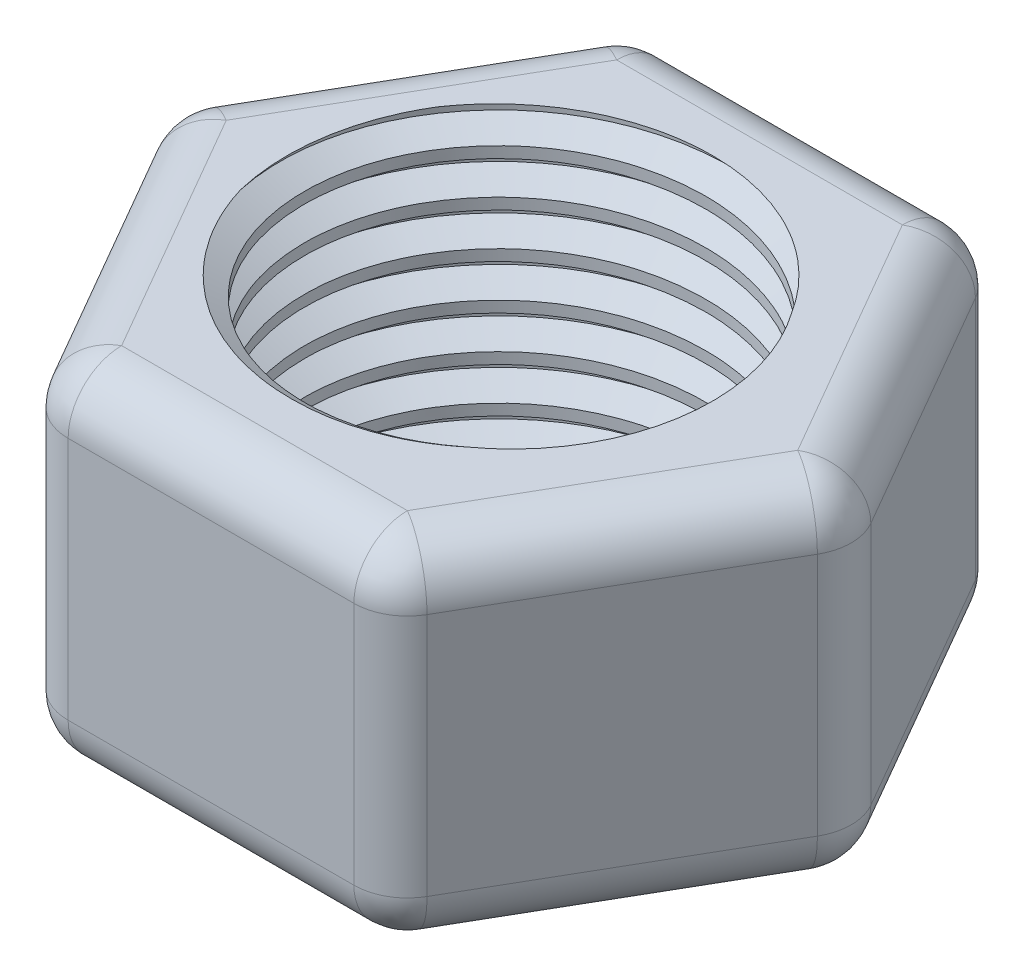
SolidWorks part; units mm, degrees
material "AISI 316 Annealed Stainless Steel Bar (SS)"
ref_plane "Front Plane" through (0, 0, 0) normal (0, 0, 1) x (1, 0, 0)
ref_plane "Top Plane" through (0, 0, 0) normal (0, 1, 0) x (1, 0, 0)
ref_plane "Right Plane" through (0, 0, 0) normal (1, 0, 0) x (0, 0, -1)
sketch "Sketch1" plane through (0, 0, 0) normal (0, 1, 0) x (1, 0, 0)
  line L1 (8.2489, 0) -> (4.1244, 7.1437)
  line L2 (4.1244, 7.1437) -> (-4.1244, 7.1437)
  line L3 (-4.1244, 7.1437) -> (-8.2489, 0)
  line L4 (-8.2489, 0) -> (-4.1244, -7.1437)
  line L5 (-4.1244, -7.1437) -> (4.1244, -7.1437)
  line L6 (4.1244, -7.1437) -> (8.2489, 0)
  circle A0 centre (0, 0) radius 7.1437 construction
  circle A1 centre (0, 0) radius 4.7625
  dimension "D2" = 9.525
  dimension "D1" = 14.2875
extrude "Boss-Extrude1" add sketch "Sketch1" along normal blind 8.3344
fillet "Fillet1" radius 1.27 18 edges at (-4.1244, 4.1672, -7.1437) (-8.2489, 4.1672, 0) (-4.1244, 4.1672, 7.1437) (4.1244, 4.1672, 7.1437) (4.1244, 4.1672, -7.1437) (8.2489, 4.1672, 0) (6.1867, 0, -3.5719) (0, 0, -7.1437) (-6.1867, 0, -3.5719) (-6.1867, 0, 3.5719) (0, 0, 7.1437) (6.1867, 0, 3.5719) (0, 8.3344, 7.1437) (-6.1867, 8.3344, 3.5719) (-6.1867, 8.3344, -3.5719) (0, 8.3344, -7.1437) (6.1867, 8.3344, -3.5719) (6.1867, 8.3344, 3.5719)
thread "Thread1" pitch 1.0583 method cut profile "Thread Profile1" start angle 0, offset 2.54, length 12.7, pitch 1.0583, diameter 9.525
ref_plane "Plane1" through (-4.7625, 10.8744, 0) normal (0, 0, 1) x (-1, 0, 0)
sketch "Thread Profile1" plane through (-4.7625, 10.8744, 0) normal (0, 0, 1) x (-1, 0, 0)
  line L0 (0, 0) -> (0, 1.0583) construction
  line L1 (0, 0) -> (0.5728, 0.3307)
  line L2 (0.5728, 0.3307) -> (0.5728, 0.463)
  line L3 (0.5728, 0.463) -> (0, 0.7937)
  line L4 (0.5728, 0.3969) -> (0, 0.3969) construction
  line L11 (0, 0) -> (0, 0.7937)
  point P2 (0, 0)
  dimension "Pitch" = 1.0583
  dimension "Profile_Angle" = 60
  dimension "Profile_Land" = 0.1323
  dimension "Profile_Height" = 0.5728
